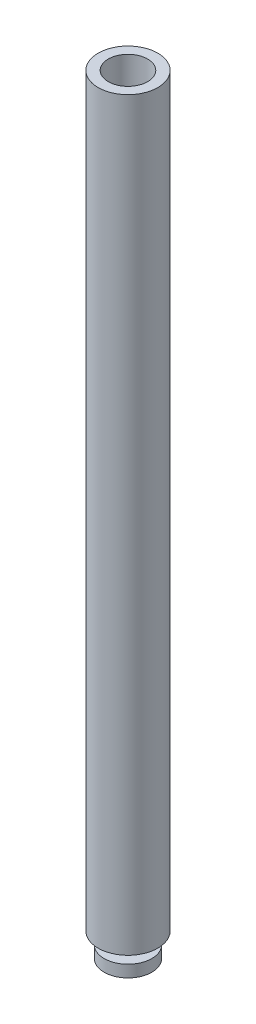
SolidWorks part; units mm, degrees
ref_plane "Front Plane" through (0, 0, 0) normal (0, 0, 1) x (1, 0, 0)
ref_plane "Top Plane" through (0, 0, 0) normal (0, 1, 0) x (1, 0, 0)
ref_plane "Right Plane" through (0, 0, 0) normal (1, 0, 0) x (0, 0, -1)
sketch "Sketch1" plane through (0, 0, 0) normal (0, 1, 0) x (1, 0, 0)
  circle A0 centre (-0.522, 0.5111) radius 2
  circle A1 centre (-0.522, 0.5111) radius 2.5
  dimension "D1" = 4
  dimension "D2" = 5
extrude "Boss-Extrude1" add sketch "Sketch1" along normal blind 62.5 contours A1
extrude "Boss-Extrude2" add sketch "Sketch1<3>" along normal blind 1 contours A0 region at (-0.522, 0, -0.5111)
sketch "Sketch1<3>" plane through (0, 0, 0) normal (0, 1, 0) x (1, 0, 0) same geometry as "Sketch1"
sketch "Sketch5" plane through (0, 0, 0) normal (0, -1, 0) x (1, 0, 0)
  circle A2 centre (-0.522, -0.5111) radius 1
  circle A3 centre (-0.522, -0.5111) radius 1
  dimension "D2" = 2
  dimension "D1" = 1.5
extrude "Boss-Extrude3" add sketch "Sketch5" along normal blind 1 contours A3
sketch "Sketch6" plane through (0, -1, 0) normal (0, -1, 0) x (1, 0, 0)
  circle A0 centre (-0.522, -0.5111) radius 2
  dimension "D1" = 4
extrude "Boss-Extrude4" add sketch "Sketch6" along normal blind 1
sketch "Sketch8" plane through (0, -2, 0) normal (0, -1, 0) x (-1, 0, 0)
  circle A0 centre (0.522, 0.5111) radius 1.5
  dimension "D1" = 3
sketch "Sketch11" plane through (0, 62.5, 0) normal (0, 1, 0) x (1, 0, 0)
  text T0 "VIII" font "Century Gothic" height in points 5
sketch "Sketch12" plane through (0, 62.5, 0) normal (0, 1, 0) x (1, 0, 0)
  circle A0 centre (-0.522, 0.5111) radius 1.65
extrude "Cut-Extrude1" cut sketch "Sketch12" against normal blind 5
